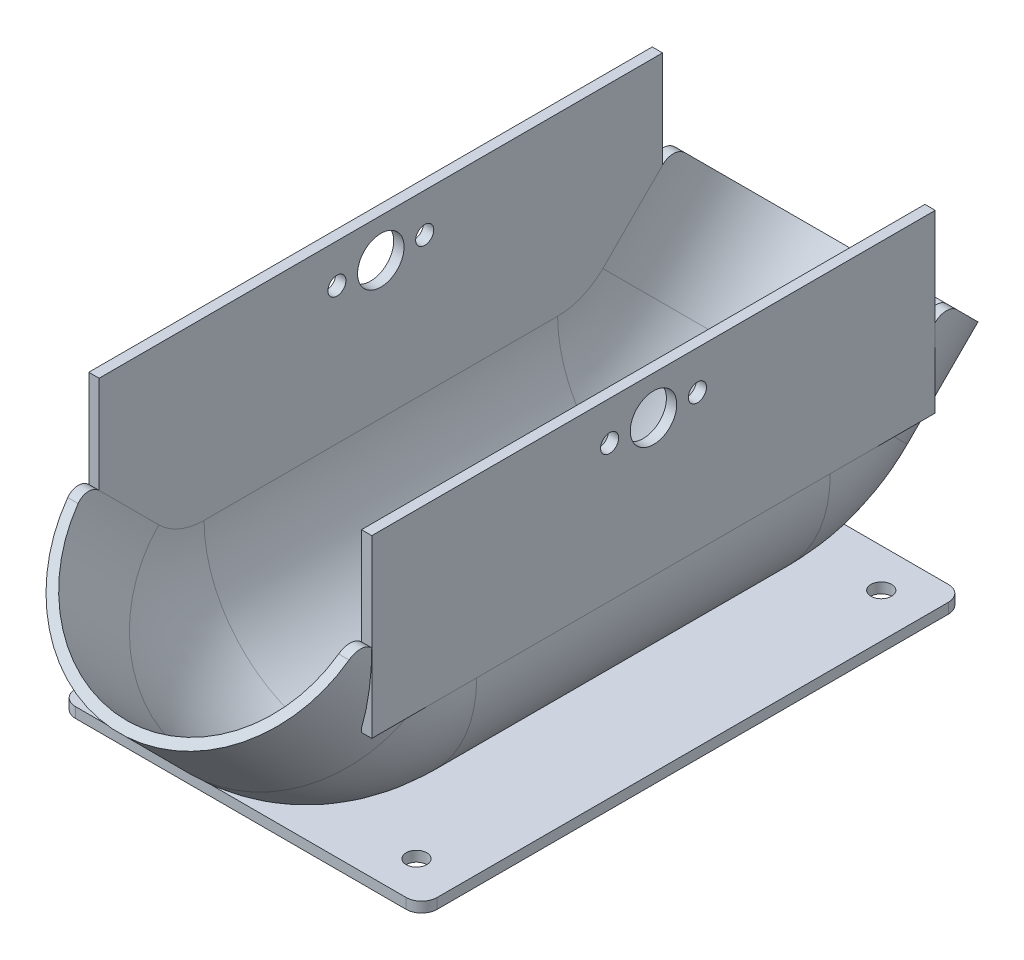
SolidWorks part; units mm, degrees
ref_plane "Front Plane" through (0, 0, 0) normal (0, 0, 1) x (1, 0, 0)
ref_plane "Top Plane" through (0, 0, 0) normal (0, 1, 0) x (1, 0, 0)
ref_plane "Right Plane" through (0, 0, 0) normal (1, 0, 0) x (0, 0, -1)
sketch "Sketch1" plane through (0, 0, 0) normal (0, 0, 1) x (1, 0, 0)
  line L2 (-25.4, 0) -> (-27.4, 0)
  line L3 (25.4, 0) -> (27.4, 0)
  line L4 (-27.3269, 2) -> (27.3269, 2) construction
  line L5 (-25.4, 0) -> (25.4, 0) construction
  arc A0 (-25.4, 0) -> (25.4, 0) centre (0, 0) ccw
  arc A1 (-27.4, 0) -> (27.4, 0) centre (0, 0) ccw
  arc A2 (-27.3269, 2) -> (27.3269, 2) centre (0, 0) ccw construction
  dimension "D1" = 50.8
  dimension "D2" = 2
sketch "Sketch3" plane through (0, 0, 0) normal (1, 0, 0) x (0, 0, -1)
  line L0 (-34.2315, -27.6128) -> (34.2315, -27.6128)
  line L2 (0, 0) -> (0, -27.4) construction
  line L3 (62.5157, -15.8971) -> (76.2, -2.2128)
  line L4 (0, -27.6128) -> (0, 7.0661) construction
  line L5 (-62.5157, -15.8971) -> (-76.2, -2.2128)
  arc A0 (34.2315, -27.6128) -> (62.5157, -15.8971) centre (34.2315, 12.3872) ccw
  arc A1 (-34.2315, -27.6128) -> (-62.5157, -15.8971) centre (-34.2315, 12.3872) cw
  point P7 (50.8, -27.6128)
  point P14 (-50.8, -27.6128)
  dimension "D3" = 40
  dimension "D1" = 45
  dimension "D2" = 50.8
  dimension "D4" = 25.4
sweep "Sweep2" add profiles "Sketch1" path "Sketch3"
sketch "Sketch4" plane through (0, 0, 0) normal (0, 1, 0) x (1, 0, 0)
  circle A0 centre (-26.5, 45) radius 2
  circle A1 centre (26.5, 45) radius 2
  circle A2 centre (-26.5, -45) radius 2
  circle A3 centre (26.5, -45) radius 2
  dimension "D3" = 4
  dimension "D4" = 4
  dimension "D5" = 4
  dimension "D6" = 4
  dimension "D1" = 53
  dimension "D2" = 90
  dimension "D7" = 45
  dimension "D8" = 26.5
sketch "Sketch5" plane through (0, 0, 0) normal (0, 1, 0) x (1, 0, 0)
  line L1 (-35, 52.5) -> (35, 52.5)
  line L2 (-35, 52.5) -> (-35, -52.5)
  line L3 (-35, -52.5) -> (35, -52.5)
  line L4 (35, 52.5) -> (35, -52.5)
  dimension "D1" = 105
  dimension "D2" = 52.5
  dimension "D3" = 70
  dimension "D4" = 35
ref_plane "Plane2" through (0, -27.4, 0) normal (0, -1, 0) x (-1, 0, 0)
sketch "Sketch6" plane through (0, -27.4, 0) normal (0, -1, 0) x (-1, 0, 0)
  line L0 (-35, 52.5) -> (35, 52.5)
  line L1 (-35, 52.5) -> (-35, -52.5)
  line L2 (-35, -52.5) -> (35, -52.5)
  line L3 (35, 52.5) -> (35, -52.5)
  dimension "D1" = 35
  dimension "D2" = 52.5
  dimension "D3" = 70
  dimension "D4" = 105
extrude "Boss-Extrude1" add sketch "Sketch6" against normal blind 2
extrude "Cut-Extrude1" cut sketch "Sketch4" against normal blind 5 from surface starting at face at (0, -25.4, 0)
fillet "Fillet1" radius 3 4 edges at (26.4, 17.3124, -56.6748) (-26.4, 17.3124, -56.6748) (26.4, 17.3124, 56.6748) (-26.4, 17.3124, 56.6748)
fillet "Fillet2" radius 3 4 edges at (35, -26.4, -52.5) (-35, -26.4, -52.5) (35, -26.4, 52.5) (-35, -26.4, 52.5)
sketch "Sketch7" plane through (0, 0, 0) normal (0, 1, 0) x (1, 0, 0)
  line L1 (-27.4, 54.5534) -> (-25.4, 54.5534)
  line L2 (-27.4, 54.5534) -> (-27.4, -54.5534)
  line L3 (-27.4, -54.5534) -> (-25.4, -54.5534)
  line L4 (-25.4, 54.5534) -> (-25.4, -54.5534)
ref_plane "Plane3" through (0, 34, 0) normal (0, 1, 0) x (1, 0, 0)
sketch "Sketch8" plane through (0, 0, 0) normal (0, 0, 1) x (1, 0, 0)
  line L0 (-27.3859, 16.0697) -> (-27.4, 0)
  arc A0 (-27.4, 0) -> (-16.5328, -21.8501) centre (-0.0482, -0.024) ccw
  arc A1 (-27.4, 0) -> (-10.2762, -25.4) centre (0, 0) ccw construction
sketch "Sketch9" plane through (0, 34, 0) normal (0, 1, 0) x (1, 0, 0)
  line L0 (0, 0) -> (0, 51.2715) construction
  line L1 (-27.4, 54.5534) -> (-25.4, 54.5534)
  line L2 (-27.4, 54.5534) -> (-27.4, -54.5534)
  line L3 (-27.4, -54.5534) -> (-25.4, -54.5534)
  line L4 (-25.4, 54.5534) -> (-25.4, -54.5534)
  line L5 (27.4, -54.5534) -> (25.4, -54.5534)
  line L6 (25.4, 54.5534) -> (25.4, -54.5534)
  line L7 (27.4, 54.5534) -> (25.4, 54.5534)
  line L8 (27.4, 54.5534) -> (27.4, -54.5534)
extrude "Boss-Extrude2" add sketch "Sketch9" against normal up to surface (34 mm away) up to face at (-26.4, 0, 0)
sketch "Sketch10" plane through (-27.4, 0, 0) normal (-1, 0, 0) x (0, 0, 1)
  line L0 (0, 0) -> (0, 20.3745) construction
  line L1 (-54.5534, 0) -> (54.5534, 0) construction
  line L2 (-54.5534, 34) -> (54.5534, 34) construction
  circle A0 centre (-8.5, 26.5) radius 1.75
  circle A1 centre (8.5, 26.5) radius 1.75
  circle A2 centre (0, 26.5) radius 4.5
  point P12 (0, 0)
  dimension "D1" = 3.5
  dimension "D4" = 9
  dimension "D2" = 7.5
  dimension "D3" = 8.5
extrude "Cut-Extrude2" cut sketch "Sketch10" against normal through all
equation "\"D7@Sketch4\"=90/2"
equation "\"D8@Sketch4\"=53/2"
equation "\"D2@Sketch5\"=105/2"
equation "\"D4@Sketch5\"=35"
